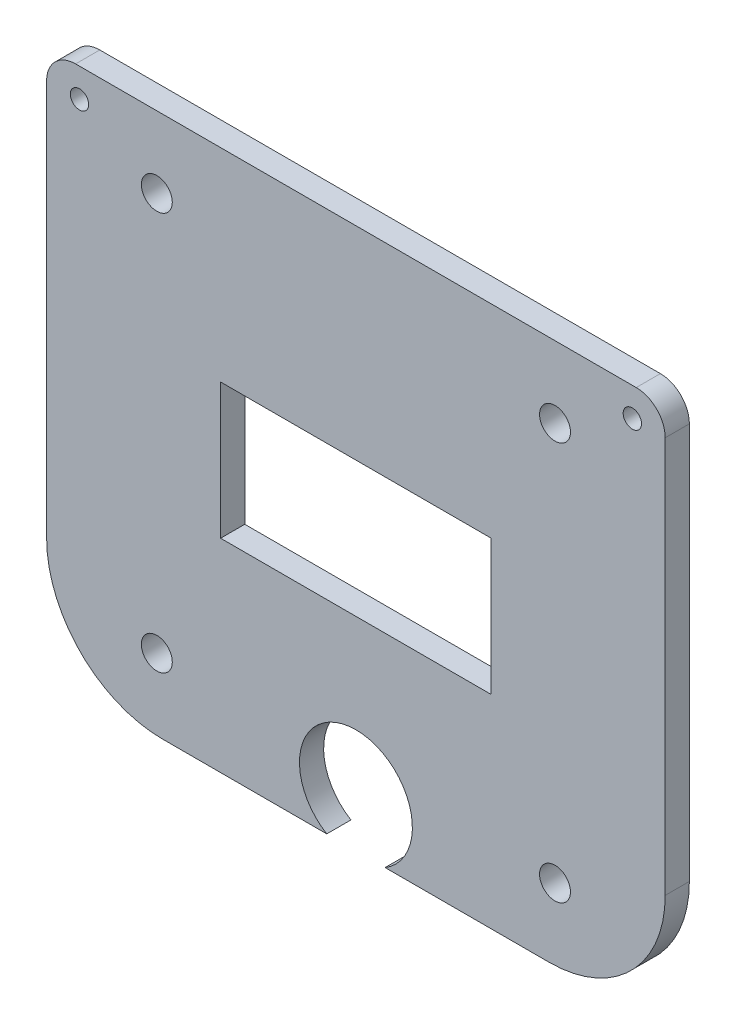
SolidWorks part; units mm, degrees
material "Delrin 2700 NC010, Low Viscosity Acetal Copolymer (SS)"
ref_plane "Front Plane" through (0, 0, 0) normal (0, 0, 1) x (1, 0, 0)
ref_plane "Top Plane" through (0, 0, 0) normal (0, 1, 0) x (1, 0, 0)
ref_plane "Right Plane" through (0, 0, 0) normal (1, 0, 0) x (0, 0, -1)
sketch "Sketch1" plane through (0, 0, 0) normal (0, 0, 1) x (1, 0, 0)
  line L0 (0, -1000) -> (0, 49000) construction
  line L1 (18.415, 17.78) -> (-18.415, 17.78)
  line L2 (20.32, 15.875) -> (20.32, -10.16)
  line L3 (12.7, -17.78) -> (-12.7, -17.78)
  line L4 (-20.32, 15.875) -> (-20.32, -10.16)
  line L5 (20.32, 17.78) -> (-20.32, -17.78) construction
  line L6 (20.32, -17.78) -> (-20.32, 17.78) construction
  line L7 (-1000, 0) -> (49000, 0) construction
  line L9 (-8.89, 4.445) -> (8.89, 4.445)
  line L10 (-8.89, 4.445) -> (-8.89, -4.445)
  line L11 (-8.89, -4.445) -> (8.89, -4.445)
  line L12 (8.89, 4.445) -> (8.89, -4.445)
  line L13 (-8.89, 4.445) -> (8.89, -4.445) construction
  line L14 (-8.89, -4.445) -> (8.89, 4.445) construction
  circle A0 centre (0, -14.605) radius 3.7084
  circle A1 centre (-18.1597, 15.8897) radius 0.6032
  circle A2 centre (-13.08, -13.08) radius 1.016
  circle A3 centre (18.1597, 15.8897) radius 0.6033
  circle A4 centre (-13.08, 13.08) radius 1.016
  circle A5 centre (13.08, 13.08) radius 1.016
  circle A6 centre (13.08, -13.08) radius 1.016
  arc A7 (-12.7, -17.78) -> (-20.32, -10.16) centre (-12.7, -10.16) cw
  arc A8 (20.32, -10.16) -> (12.7, -17.78) centre (12.7, -10.16) cw
  arc A9 (-18.415, 17.78) -> (-20.32, 15.875) centre (-18.415, 15.875) ccw
  arc A10 (18.415, 17.78) -> (20.32, 15.875) centre (18.415, 15.875) cw
  point P0 (0, 0)
  point P9 (0, 0)
  dimension "D6" = 7.4168
  dimension "D7" = 1.2065
  dimension "D9" = 2.032
  dimension "D12" = 7.62
  dimension "D13" = 7.62
  dimension "D14" = 1.905
  dimension "D15" = 1.905
  dimension "D1" = 35.56
  dimension "D2" = 40.64
  dimension "D3" = 8.89
  dimension "D4" = 17.78
  dimension "D5" = 3.175
  dimension "D8" = 24.13
  dimension "D10" = 13.08
  dimension "D11" = 13.08
extrude "Boss-Extrude1" add sketch "Sketch1" along normal blind 1.5875 contours A10 L1 A9 L4 A7 L3 A0 A8 L2 A6 A5 A4 L9 L12 L11 L10 A1 A2 A3 region at (19.3802, 16.8402, 0)
ref_axis "Axis1" through (0, 0, 0) along (0, 0, 1)
